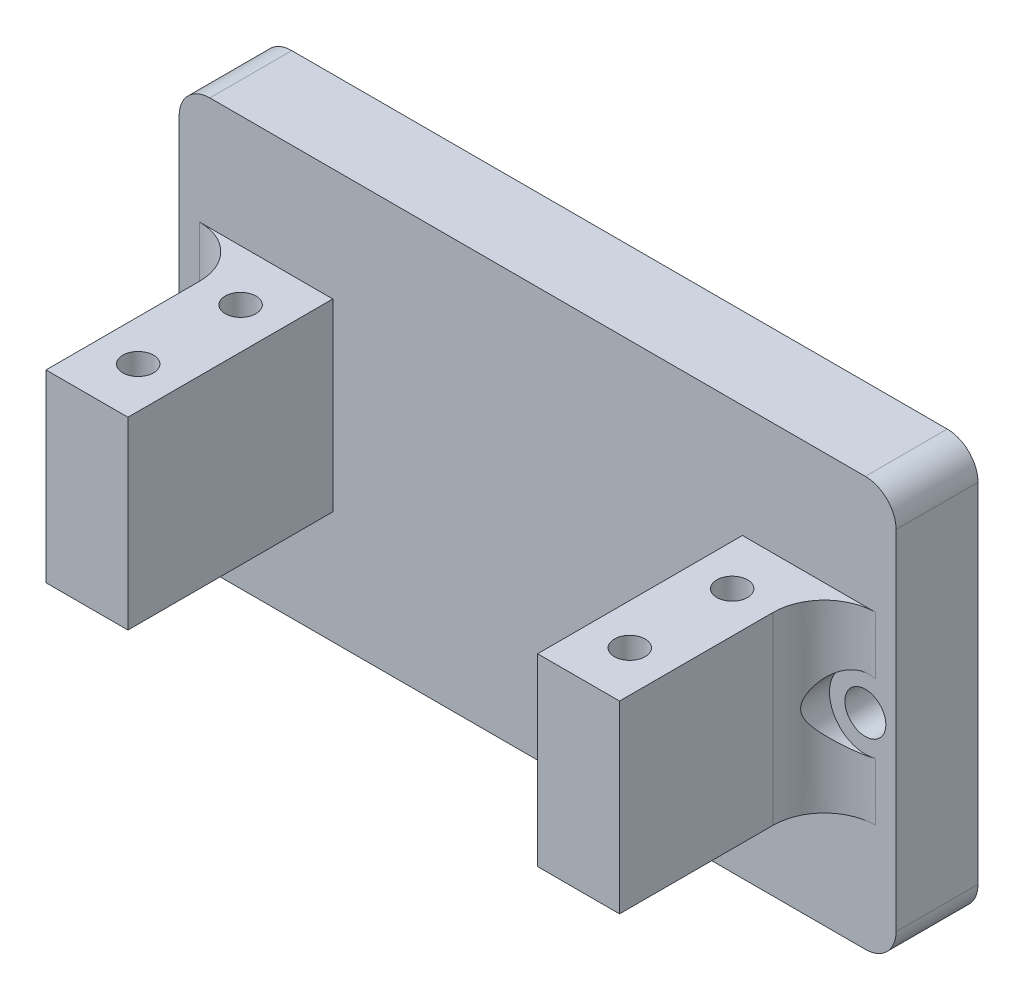
SolidWorks part; units mm, degrees
ref_plane "Ön Düzlem" through (0, 0, 0) normal (0, 0, 1) x (1, 0, 0)
ref_plane "Üst Düzlem" through (0, 0, 0) normal (0, 1, 0) x (1, 0, 0)
ref_plane "Sağ Düzlem" through (0, 0, 0) normal (1, 0, 0) x (0, 0, -1)
sketch "Çizim1" plane through (0, 0, 0) normal (0, 0, 1) x (1, 0, 0)
  line L1 (-32, 20) -> (32, 20)
  line L2 (-35, 17) -> (-35, -17)
  line L3 (-32, -20) -> (32, -20)
  line L4 (35, 17) -> (35, -17)
  line L5 (-35, 20) -> (35, -20) construction
  line L6 (-35, -20) -> (35, 20) construction
  arc A0 (32, -20) -> (35, -17) centre (32, -17) ccw
  arc A1 (-32, -20) -> (-35, -17) centre (-32, -17) cw
  arc A2 (35, 17) -> (32, 20) centre (32, 17) ccw
  arc A3 (-35, 17) -> (-32, 20) centre (-32, 17) cw
  point P0 (0, 0)
  dimension "D3" = 3
  dimension "D1" = 40
  dimension "D2" = 70
extrude "Yükseklik-Ekstrüzyon1" add sketch "Çizim1" along normal blind 8
sketch "Çizim3" plane through (0, 0, 8) normal (0, 0, 1) x (1, 0, 0)
  line L0 (0, 0) -> (0, 25.6569) construction
  circle A0 centre (-32, 0) radius 2
  circle A1 centre (32, 0) radius 2
  dimension "D1" = 4
  dimension "D2" = 32
extrude "Kes-Ekstrüzyon1" cut sketch "Çizim3" against normal blind 20
sketch "Çizim4" plane through (0, 0, 8) normal (0, 0, 1) x (1, 0, 0)
  line L0 (-46.6557, 0) -> (47.8966, 0) construction
  line L1 (28, -9) -> (28, 0)
  line L2 (-28, -9) -> (-28, 0)
  line L3 (28, 0) -> (28, 9)
  line L4 (28, 9) -> (20, 9)
  line L5 (20, 9) -> (20, 0)
  line L6 (20, 0) -> (20, -9)
  line L7 (20, -9) -> (28, -9)
  line L8 (-28, 0) -> (-28, 9)
  line L9 (-28, 9) -> (-20, 9)
  line L10 (-20, 9) -> (-20, 0)
  line L11 (-20, 0) -> (-20, -9)
  line L12 (-20, -9) -> (-28, -9)
  point P14 (-20, 4.5)
  dimension "D1" = 9
  dimension "D2" = 20
  dimension "D3" = 8
  dimension "D4" = 9
  dimension "D5" = 20
  dimension "D6" = 8
extrude "Yükseklik-Ekstrüzyon2" add sketch "Çizim4" along normal blind 20
sketch "Çizim5" plane through (0, -9, 0) normal (0, -1, 0) x (1, 0, 0)
  line L0 (-28, 18) -> (-20, 18) construction
  line L1 (-24, 28) -> (-24, 8) construction
  line L2 (-28, 28) -> (-20, 28) construction
  line L3 (-28, 8) -> (-20, 8) construction
  line L4 (24, 28) -> (24, 8) construction
  line L5 (20, 28) -> (28, 28) construction
  line L6 (20, 8) -> (28, 8) construction
  line L7 (-28, 28) -> (-28, 8) construction
  line L8 (-20, 28) -> (-20, 8) construction
  line L9 (20, 18) -> (28, 18) construction
  line L10 (20, 28) -> (20, 8) construction
  line L11 (28, 28) -> (28, 8) construction
  circle A2 centre (-24, 23) radius 1.5
  circle A3 centre (-24, 13) radius 1.5
  circle A4 centre (24, 23) radius 1.5
  circle A6 centre (24, 13) radius 1.5
  dimension "D2" = 3
  dimension "D4" = 3
  dimension "D5" = 5
  dimension "D1" = 3
  dimension "D3" = 3
  dimension "D6" = 5
  dimension "D7" = 5
  dimension "D8" = 5
extrude "Kes-Ekstrüzyon2" cut sketch "Çizim5" against normal blind 49
fillet "Radyus1" radius 5 1 edges at (28, 0, 8)
fillet "Radyus2" radius 5 1 edges at (-28, 0, 8)
sketch "Çizim7" plane through (0, 0, 8) normal (0, 0, 1) x (1, 0, 0)
  circle A0 centre (32, 0) radius 3.5
  dimension "D1" = 7
extrude "Kes-Ekstrüzyon3" cut sketch "Çizim7" along normal blind 10 contours A0
sketch "Çizim8" plane through (0, 0, 8) normal (0, 0, 1) x (1, 0, 0)
  circle A0 centre (-32, 0) radius 3.5
  dimension "D1" = 7
extrude "Kes-Ekstrüzyon4" cut sketch "Çizim8" along normal blind 10
